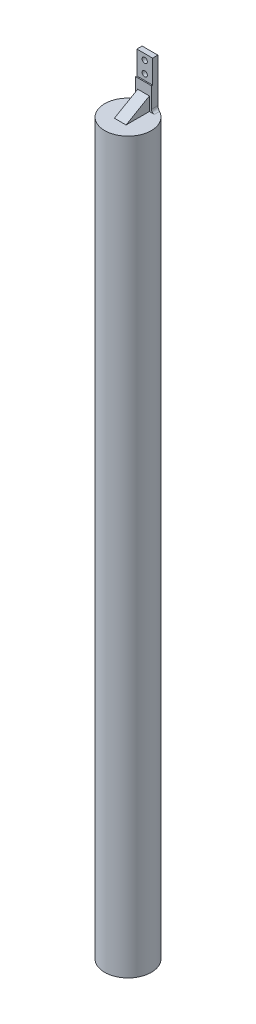
SolidWorks part; units mm, degrees
ref_plane "Front Plane" through (0, 0, 0) normal (0, 0, 1) x (1, 0, 0)
ref_plane "Top Plane" through (0, 0, 0) normal (0, 1, 0) x (1, 0, 0)
ref_plane "Right Plane" through (0, 0, 0) normal (1, 0, 0) x (0, 0, -1)
sketch "Sketch1" plane through (0, 0, 0) normal (0, 1, 0) x (1, 0, 0)
  line L1 (-1.35, 0.55) -> (1.35, 0.55)
  line L2 (-1.35, 0.55) -> (-1.35, -0.55)
  line L3 (-1.35, -0.55) -> (1.35, -0.55)
  line L4 (1.35, 0.55) -> (1.35, -0.55)
  line L5 (-1.35, 0.55) -> (1.35, -0.55) construction
  line L6 (-1.35, -0.55) -> (1.35, 0.55) construction
  point P0 (0, 0)
  dimension "D1" = 2.7
  dimension "D2" = 1.1
extrude "Boss-Extrude1" add sketch "Sketch1" along normal blind 4
sketch "Sketch2" plane through (0, 4, 0) normal (0, 1, 0) x (1, 0, 0)
  line L15 (1.35, -0.55) -> (1.35, 0.55) construction
  line L16 (-1.35, 0.55) -> (1.35, 0.55)
  line L17 (-1.35, 0.55) -> (-1.35, -0.35)
  line L18 (-1.35, -0.35) -> (1.35, -0.35)
  line L19 (1.35, 0.55) -> (1.35, -0.35)
  dimension "D1" = 0.9
extrude "Boss-Extrude2" add sketch "Sketch2" along normal blind 4
sketch "Sketch3" plane through (0, 0, 0) normal (0, -1, 0) x (1, 0, 0)
  line L1 (-1.35, -0.55) -> (1.35, -0.55)
  circle A1 centre (0, 3.2153) radius 4
  line M1 (1.35, -0.55) -> (1.35, 0.55)
  line M2 (1.35, 0.55) -> (-1.35, 0.55)
  line M3 (-1.35, 0.55) -> (-1.35, -0.55)
  line M4 (-1.35, -0.55) -> (1.35, -0.55)
  dimension "D1" = 8
extrude "lenght extrusion" add sketch "Sketch3" along normal blind 125 contours A1 M1 M3 M2 | M4 M1 M2 M3 region at (0, 0, 0) region at (0, 0, 3.454)
sketch "Sketch6" plane through (0, 0, 0) normal (1, 0, 0) x (0, 0, -1)
  line L0 (-0.55, 2.3094) -> (-4.55, 0)
  line L1 (-0.55, 4) -> (-0.55, 0) construction
  line L3 (-4.55, 0) -> (-0.55, 0)
  line L5 (-0.55, 0) -> (-0.55, 2.3094)
  dimension "D1" = 30
  dimension "D2" = 4
extrude "Boss-Extrude4" add sketch "Sketch6" along normal mid plane 2
fillet "Fillet8" radius 0.5 2 edges at (1.35, 0, 0) (-1.35, 0, 0)
sketch "Sketch7" plane through (0, 0, 0.35) normal (0, 0, 1) x (1, 0, 0)
  line L0 (-1.35, 4) -> (1.35, 4) construction
  circle A0 centre (0, 5) radius 0.45
  circle A4 centre (0, 7) radius 0.45
  dimension "D1" = 0.9
  dimension "D4" = 0.9
  dimension "D5" = 0
  dimension "D2" = 0
  dimension "D3" = 1
  dimension "D6" = 2
extrude "Cut-Extrude1" cut sketch "Sketch7" against normal up to surface (0.9 mm away) up to face at (0, -38.8333, -0.55)
